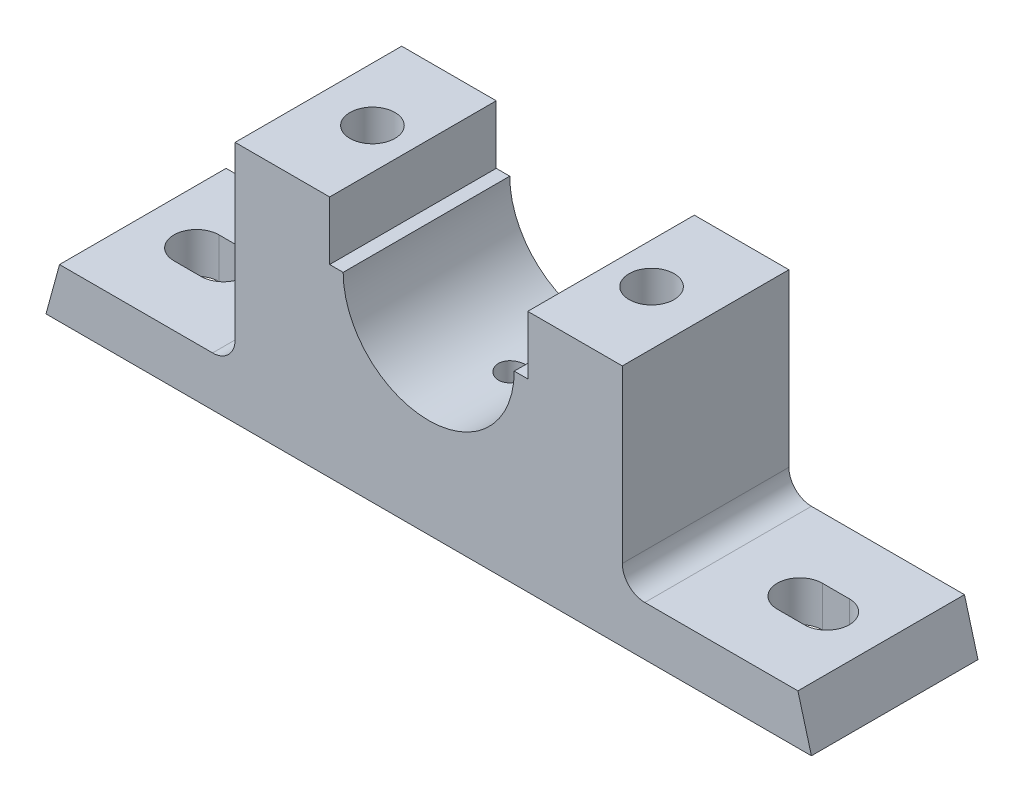
SolidWorks part; units mm, degrees
ref_plane "Front Plane" through (0, 0, 0) normal (0, 0, 1) x (1, 0, 0)
ref_plane "Top Plane" through (0, 0, 0) normal (0, 1, 0) x (1, 0, 0)
ref_plane "Right Plane" through (0, 0, 0) normal (1, 0, 0) x (0, 0, -1)
other "Center of Mass"
sketch "Sketch1" plane through (0, 0, 0) normal (0, 0, 1) x (1, 0, 0)
  line L0 (85, 0) -> (-85, 0)
  line L1 (-85, 0) -> (-82, 11)
  line L3 (-48, 11) -> (-82, 11)
  line L4 (-22, 54) -> (-43, 54)
  line L5 (-22, 54) -> (-22, 41)
  line L6 (-22, 41) -> (-19, 41)
  line L7 (-43, 54) -> (-43, 16)
  line L8 (22, 54) -> (22, 41)
  line L9 (22, 41) -> (19, 41)
  line L10 (85, 0) -> (82, 11)
  line L11 (48, 11) -> (82, 11)
  line L12 (22, 54) -> (43, 54)
  line L13 (43, 54) -> (43, 16)
  arc A0 (-48, 11) -> (-43, 16) centre (-48, 16) ccw
  arc A1 (-19, 41) -> (19, 41) centre (0, 41) ccw
  arc A2 (48, 11) -> (43, 16) centre (48, 16) cw
  dimension "D1" = 5
extrude "Boss-Extrude1" add sketch "Sketch1" along normal blind 37
sketch "Sketch2" plane through (0, 0, 0) normal (0, 1, 0) x (1, 0, 0)
  line L6 (-77, -7.5) -> (-77, -29.5)
  line L7 (-77, -29.5) -> (-4, -29.5)
  line L8 (4, -7.5) -> (4, -29.5)
  line L9 (-4, -7.5) -> (-4, -29.5)
  line L10 (-77, -7.5) -> (-4, -7.5)
  line L11 (77, -7.5) -> (4, -7.5)
  line L12 (77, -7.5) -> (77, -29.5)
  line L13 (77, -29.5) -> (4, -29.5)
extrude "Cut-Extrude2" cut sketch "Sketch2" along normal blind 2
chamfer "Chamfer1" distance 2 angle 45 1 edges at (-77, 2, 18.5)
chamfer "Chamfer2" distance 2 angle 45 1 edges at (4, 2, 18.5)
chamfer "Chamfer3" distance 2 angle 45 1 edges at (-4, 2, 18.5)
chamfer "Chamfer4" distance 2 angle 45 1 edges at (77, 2, 18.5)
sketch "Sketch3" plane through (0, 0, 0) normal (0, 1, 0) x (1, 0, 0)
  line L0 (0, 0) -> (0, -37)
  line L1 (-85, -37) -> (85, -37) construction
  line L5 (-41, -28.5) -> (-21, -28.5)
  line L6 (-41, -28.5) -> (-41, -8.5)
  line L7 (-41, -8.5) -> (-21, -8.5)
  line L8 (-21, -28.5) -> (-21, -8.5)
  line L9 (-41, -28.5) -> (-21, -8.5) construction
  line L10 (-41, -8.5) -> (-21, -28.5) construction
  line L11 (41, -8.5) -> (21, -8.5)
  line L15 (41, -28.5) -> (21, -28.5)
  line L16 (41, -28.5) -> (41, -8.5)
  line L17 (21, -28.5) -> (21, -8.5)
extrude "Cut-Extrude4" cut sketch "Sketch3" along normal blind 8 contours L5 L8 L7 L6 | L17 L15 L16 L11 region at (-31, 0, 18.5) region at (31, 0, 18.5)
sketch "Sketch5" plane through (0, 2, 0) normal (0, -1, 0) x (1, 0, 0)
  line L2 (70, 18.5821) -> (64, 18.5821) construction
  line L3 (70, 23.5821) -> (64, 23.5821)
  line L4 (70, 13.5821) -> (64, 13.5821)
  line L6 (-70, 18.5821) -> (-64, 18.5821) construction
  line L7 (-70, 23.5821) -> (-64, 23.5821)
  line L8 (-70, 13.5821) -> (-64, 13.5821)
  arc A0 (-70, 23.5821) -> (-70, 13.5821) centre (-70, 18.5821) ccw
  arc A1 (-64, 13.5821) -> (-64, 23.5821) centre (-64, 18.5821) ccw
  arc A2 (70, 23.5821) -> (70, 13.5821) centre (70, 18.5821) cw
  arc A3 (64, 13.5821) -> (64, 23.5821) centre (64, 18.5821) cw
  point P5 (-67, 18.5821)
  point P9 (67, 18.5821)
extrude "Cut-Extrude5" cut sketch "Sketch5" against normal through all
sketch "Sketch6" plane through (0, 54, 0) normal (0, 1, 0) x (1, 0, 0)
  circle A0 centre (-31, -18.5) radius 5
  circle A1 centre (31, -18.5) radius 5
extrude "Cut-Extrude6" cut sketch "Sketch6" against normal through all
ref_axis "Axis1" through (-43, 16, 37) along (0, 1, 0)
ref_plane "Plane1" through (0, 16, 0) normal (0, 1, 0) x (1, 0, 0)
sketch "Sketch8" plane through (0, 16, 0) normal (0, 1, 0) x (1, 0, 0)
  circle A0 centre (0, -18.5) radius 3
extrude "Cut-Extrude7" cut sketch "Sketch8" along normal blind 21 and the other way blind 2
